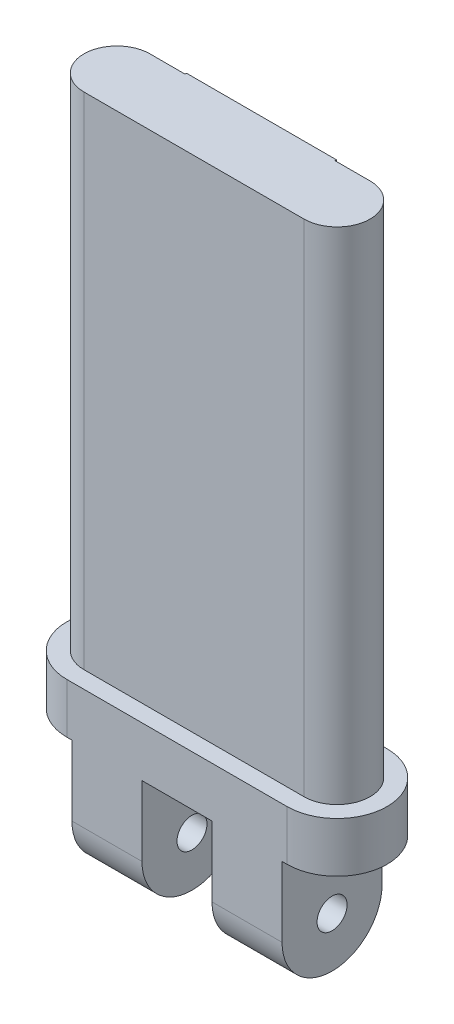
SolidWorks part; units mm, degrees
ref_plane "前视基准面" through (0, 0, 0) normal (0, 0, 1) x (1, 0, 0)
ref_plane "上视基准面" through (0, 0, 0) normal (0, 1, 0) x (1, 0, 0)
ref_plane "右视基准面" through (0, 0, 0) normal (1, 0, 0) x (0, 0, -1)
sketch "草图1" plane through (0, 0, 0) normal (0, 1, 0) x (1, 0, 0)
  line L3 (-11, 3.3) -> (11, 3.3)
  line L4 (-11, -3.3) -> (11, -3.3)
  arc A2 (11, -3.3) -> (11, 3.3) centre (11, 0) ccw
  arc A3 (-11, 3.3) -> (-11, -3.3) centre (-11, 0) ccw
extrude "凸台-拉伸1" add sketch "草图1" along normal blind 50
sketch "草图2" plane through (0, 0, -3.3) normal (0, 0, -1) x (-1, 0, 0)
  line L0 (-11, 25) -> (11, 25) construction
  line L1 (-11, 50) -> (-11, 0) construction
  line L2 (11, 50) -> (11, 0) construction
  line L3 (-8.1204, 25) -> (-8.1204, 12.5) construction
  line L4 (-11, 12.5) -> (11, 12.5) construction
  line L5 (-11, 37.5) -> (11, 37.5) construction
  line L6 (0, 37.5) -> (0, 12.5) construction
  line L8 (-7.5, 36.75) -> (7.5, 36.75)
  line L9 (-7.5, 36.75) -> (-7.5, 38.25)
  line L10 (-7.5, 38.25) -> (7.5, 38.25)
  line L11 (7.5, 36.75) -> (7.5, 38.25)
  line L12 (-7.5, 36.75) -> (7.5, 38.25) construction
  line L13 (-7.5, 38.25) -> (7.5, 36.75) construction
  line L14 (-7.5, 13.25) -> (7.5, 13.25)
  line L15 (-7.5, 13.25) -> (-7.5, 11.75)
  line L16 (-7.5, 11.75) -> (7.5, 11.75)
  line L17 (7.5, 13.25) -> (7.5, 11.75)
  line L18 (-7.5, 13.25) -> (7.5, 11.75) construction
  line L19 (-7.5, 11.75) -> (7.5, 13.25) construction
  line L20 (-7.5, 25.75) -> (7.5, 25.75)
  line L21 (-7.5, 25.75) -> (-7.5, 24.25)
  line L22 (-7.5, 24.25) -> (7.5, 24.25)
  line L23 (7.5, 25.75) -> (7.5, 24.25)
  line L24 (-7.5, 25.75) -> (7.5, 24.25) construction
  line L25 (-7.5, 24.25) -> (7.5, 25.75) construction
  point P22 (0, 25)
  dimension "D1" = 12.5
  dimension "D2" = 1.5
  dimension "D3" = 15
  dimension "D4" = 1.5
  dimension "D5" = 15
  dimension "D6" = 1.5
  dimension "D7" = 15
extrude "切除-拉伸1" cut sketch "草图2" against normal blind 0.2
sketch "草图4" plane through (7.5, 0, 0) normal (-1, 0, 0) x (0, 0, 1)
  line L1 (-3.3, 11.75) -> (-3.3, 11.25) construction
  line L3 (-3.3, 36.75) -> (-3.3, 36.25)
  line L4 (-3.3, 24.25) -> (-3.3, 23.75)
  line L5 (-3.3, 11.75) -> (-3.3, 11.25)
  line L6 (-3.1, 11.75) -> (-3.3, 11.75)
  line L7 (-3.1, 24.25) -> (-3.3, 24.25)
  line L8 (-3.1, 36.75) -> (-3.3, 36.75)
  arc A0 (-3.1, 11.75) -> (-3.3, 11.25) centre (-6.229, 12.7116) cw
  arc A1 (-3.1, 24.25) -> (-3.3, 23.75) centre (-6.229, 25.2116) cw
  arc A2 (-3.1, 36.75) -> (-3.3, 36.25) centre (-6.229, 37.7116) cw
  dimension "D3" = 3.2734
  dimension "D1" = 0.5
  dimension "D2" = 3
sketch "草图5" plane through (0, 0, -3.3) normal (0, 0, -1) x (-1, 0, 0)
  line L0 (-7.5, 38.25) -> (-7.5, 50) construction
  line L1 (-11, 50) -> (11, 50) construction
  line L3 (-7.5, 50) -> (7.5, 50)
  line L4 (-7.5, 50) -> (-7.5, 48.5)
  line L5 (-7.5, 48.5) -> (7.5, 48.5)
  line L6 (7.5, 50) -> (7.5, 48.5)
  dimension "D1" = 15
  dimension "D2" = 1.5
sketch "草图7" plane through (0, 0, -3.3) normal (0, 0, -1) x (-1, 0, 0)
extrude "凸台-拉伸2" add sketch "草图5" along normal blind 0.15
sketch "草图8" plane through (0, 0, 0) normal (0, -1, 0) x (1, 0, 0)
  line L8 (-11, -5) -> (11, -5)
  line L9 (11, 5) -> (-11, 5)
  line L10 (-11, -5) -> (11, -5)
  line L11 (11, 5) -> (-11, 5)
  arc A8 (-11, 5) -> (-11, -5) centre (-11, 0) ccw
  arc A9 (11, -5) -> (11, 5) centre (11, 0) ccw
  arc A10 (-11, 5) -> (-11, -5) centre (-11, 0) ccw
  arc A11 (11, -5) -> (11, 5) centre (11, 0) ccw
  dimension "D2" = 1.7
extrude "凸台-拉伸4" add sketch "草图8" along normal blind 5
sketch "草图9" plane through (0, -5, 0) normal (0, -1, 0) x (1, 0, 0)
  line L0 (0, 5) -> (0, -5) construction
  line L1 (11, 5) -> (-11, 5) construction
  line L2 (-11, -5) -> (11, -5) construction
  line L7 (3.5, -5) -> (3.5, 5)
  line L9 (-3.5, -5) -> (-3.5, 5)
  line L10 (-3.5, -5) -> (-10.5, -5)
  line L11 (-3.5, -5) -> (-3.5, 5)
  line L12 (-3.5, 5) -> (-10.5, 5)
  line L13 (-10.5, -5) -> (-10.5, 5)
  line L14 (3.5, 5) -> (10.5, 5)
  line L15 (3.5, 5) -> (3.5, -5)
  line L16 (3.5, -5) -> (10.5, -5)
  line L17 (10.5, 5) -> (10.5, -5)
  line M13 (-11, -5) -> (11, -5)
  line M15 (11, 5) -> (-11, 5)
  dimension "D1" = 10
  dimension "D2" = 3.5
  dimension "D3" = 7
  dimension "D4" = 7
  dimension "D5" = 7
  dimension "D6" = 10
extrude "凸台-拉伸5" add sketch "草图9" along normal blind 12 contours L13 L9 M13 M15 | L17 L7 M15 M13 region at (7, -5, 0) region at (-7, -5, 0)
fillet "圆角2" radius 5 4 edges at (7, -17, 5) (7, -17, -5) (-7, -17, 5) (-7, -17, -5)
sketch "草图10" plane through (10.5, 0, 0) normal (1, 0, 0) x (0, 0, -1)
  line L3 (-5, -5) -> (-5, -12)
  line L4 (5, -12) -> (5, -5)
  line L5 (5, -5) -> (-5, -5)
  circle A0 centre (0, -12) radius 1.5
  arc A2 (-5, -12) -> (0, -17) centre (0, -12) ccw
  arc A3 (0, -17) -> (5, -12) centre (0, -12) ccw
  arc A4 (-5, -12) -> (0, -17) centre (0, -12) ccw
  arc A5 (0, -17) -> (5, -12) centre (0, -12) ccw
  dimension "D2" = 3
  dimension "D1" = 0
extrude "切除-拉伸3" cut sketch "草图10" against normal through all contours A0 region at (10.5, -12, 0)
sketch "草图11" plane through (-7.5, 0, 0) normal (1, 0, 0) x (0, 0, -1)
  line L0 (3.1, 36.75) -> (3.1, 38.25) construction
  line L1 (3.1, 38.25) -> (3.3, 38.25) construction
  line L2 (3.3, 38.45) -> (3.3, 38.25)
  line L3 (3.3, 36.75) -> (3.3, 36.55)
  line L4 (3.3, 38.25) -> (3.1, 38.25)
  line L5 (3.1, 36.75) -> (3.3, 36.75)
  line L6 (3.3, 25.95) -> (3.3, 25.75)
  line L7 (3.3, 25.75) -> (3.1, 25.75)
  line L8 (3.3, 13.45) -> (3.3, 13.25)
  line L9 (3.3, 13.25) -> (3.1, 13.25)
  line L10 (3.3, 24.25) -> (3.3, 24.05)
  line L11 (3.1, 24.25) -> (3.3, 24.25)
  line L12 (3.3, 11.75) -> (3.3, 11.55)
  line L13 (3.1, 11.75) -> (3.3, 11.75)
  arc A0 (3.1, 38.25) -> (3.3, 38.45) centre (3.3, 38.25) cw
  arc A1 (3.1, 36.75) -> (3.3, 36.55) centre (3.3, 36.75) ccw
  arc A2 (3.1, 25.75) -> (3.3, 25.95) centre (3.3, 25.75) cw
  arc A3 (3.1, 13.25) -> (3.3, 13.45) centre (3.3, 13.25) cw
  arc A4 (3.1, 24.25) -> (3.3, 24.05) centre (3.3, 24.25) ccw
  arc A5 (3.1, 11.75) -> (3.3, 11.55) centre (3.3, 11.75) ccw
  point P15 (0, 0)
  point P28 (0, 0)
extrude "切除-拉伸4" cut sketch "草图11" along normal blind 15
